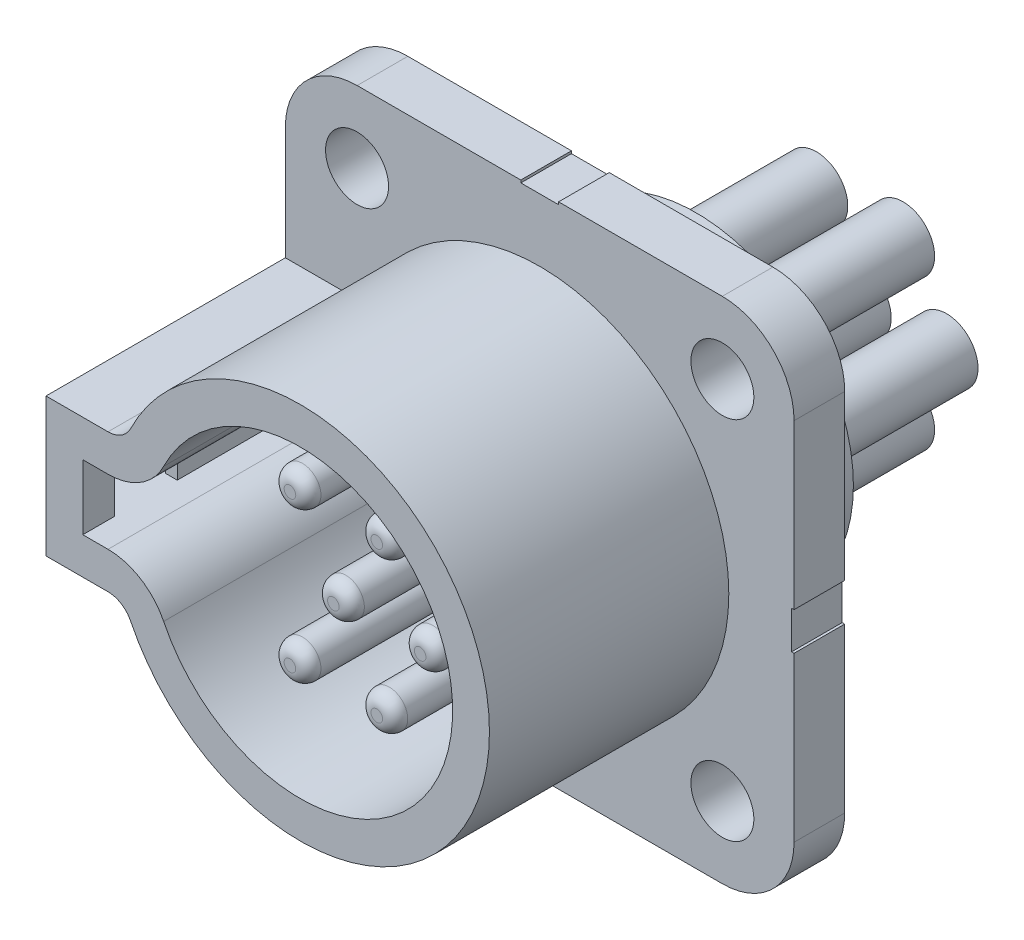
SolidWorks part; units mm, degrees
ref_plane "Front Plane" through (0, 0, 0) normal (0, 0, 1) x (1, 0, 0)
ref_plane "Top Plane" through (0, 0, 0) normal (0, 1, 0) x (1, 0, 0)
ref_plane "Right Plane" through (0, 0, 0) normal (1, 0, 0) x (0, 0, -1)
sketch "Sketch1" plane through (0, 0, 0) normal (0, 0, 1) x (1, 0, 0)
  line L1 (-10.095, 10.095) -> (10.095, 10.095)
  line L2 (-10.095, 10.095) -> (-10.095, -10.095)
  line L3 (-10.095, -10.095) -> (10.095, -10.095)
  line L4 (10.095, 10.095) -> (10.095, -10.095)
  line L5 (-10.095, 10.095) -> (10.095, -10.095) construction
  line L6 (-10.095, -10.095) -> (10.095, 10.095) construction
  point P0 (0, 0)
  dimension "D1" = 20.19
  dimension "D2" = 20.19
extrude "Boss-Extrude1" add sketch "Sketch1" along normal blind 2.01
sketch "Sketch2" plane through (0, 0, 2.01) normal (0, 0, 1) x (1, 0, 0)
  line L0 (0, 0) -> (0, 10.095) construction
  line L1 (10.095, 10.095) -> (-10.095, 10.095) construction
  line L2 (0, 0) -> (-10.095, 0) construction
  line L3 (-10.095, 10.095) -> (-10.095, -10.095) construction
  circle A0 centre (-7.25, 7.25) radius 1.25
  circle A1 centre (7.25, 7.25) radius 1.25
  circle A2 centre (7.25, -7.25) radius 1.25
  circle A3 centre (-7.25, -7.25) radius 1.25
  dimension "D1" = 2.5
  dimension "D2" = 7.25
  dimension "D3" = 7.25
extrude "Cut-Extrude1" cut sketch "Sketch2" against normal up to surface (2.01 mm away) up to face at (0, 0, 0)
fillet "Fillet1" radius 2.85 4 edges at (10.095, -10.095, 1.005) (-10.095, -10.095, 1.005) (10.095, 10.095, 1.005) (-10.095, 10.095, 1.005)
sketch "Sketch4" plane through (0, 0, 2.01) normal (0, 0, 1) x (1, 0, 0)
  line L0 (-10.095, -2.7495) -> (-10.095, 2.7495)
  line L1 (-10.095, 7.245) -> (-10.095, -7.245) construction
  line L2 (-10.095, 2.7495) -> (-7.6339, 2.7495)
  line L3 (-10.095, 0) -> (11.2357, 0) construction
  line L4 (-10.095, -2.7495) -> (-7.6339, -2.7495)
  line L5 (-8.635, -1.2895) -> (-8.635, 1.2895)
  line L6 (-8.635, 1.2895) -> (-7.6339, 1.2895)
  line L7 (-8.635, -1.2895) -> (-7.6339, -1.2895)
  line L8 (0, 10.095) -> (0, -11.6505) construction
  line L9 (7.245, 10.095) -> (-7.245, 10.095) construction
  line L10 (0, 6.045) -> (3.3385, 6.045) construction
  line L11 (0, -6.045) -> (3.3385, -6.045) construction
  line L12 (0, -7.505) -> (3.9298, -7.505) construction
  line L13 (0, 7.505) -> (4.2254, 7.505) construction
  arc A0 (-6.7363, 3.3086) -> (-6.7363, -3.3086) centre (0, 0) cw
  arc A1 (-6.7363, 3.3086) -> (-7.6339, 2.7495) centre (-7.6339, 3.7495) cw
  arc A2 (-6.7363, -3.3086) -> (-7.6339, -2.7495) centre (-7.6339, -3.7495) ccw
  arc A3 (-5.4259, 2.665) -> (-7.6339, 1.2895) centre (-7.6339, 3.7495) cw
  arc A4 (-5.4259, 2.665) -> (-5.4259, -2.665) centre (0, 0) cw
  arc A5 (-5.4259, -2.665) -> (-7.6339, -1.2895) centre (-7.6339, -3.7495) ccw
  dimension "D1" = 1
  dimension "D3" = 15.01
  dimension "D4" = 12.09
extrude "Boss-Extrude2" add sketch "Sketch4" along normal blind 9.5
sketch "Sketch5" plane through (-10.095, 0, 0) normal (-1, 0, 0) x (0, 0, 1)
  line L0 (0, 7.245) -> (0, -7.245) construction
  line L1 (0, 1.2895) -> (10.26, 1.2895)
  line L2 (0, 1.2895) -> (0, -1.2895)
  line L3 (0, -1.2895) -> (10.26, -1.2895)
  line L4 (10.26, 1.2895) -> (10.26, -1.2895)
  line L6 (0, 0) -> (-1.0293, 0) construction
  line L7 (11.51, 2.7495) -> (11.51, -2.7495) construction
  line L8 (11.51, 2.7495) -> (2.01, 2.7495) construction
  line L9 (11.51, -2.7495) -> (2.01, -2.7495) construction
  dimension "D1" = 1.25
  dimension "D2" = 1.46
  dimension "D3" = 1.46
extrude "Cut-Extrude2" cut sketch "Sketch5" against normal blind 1
sketch "Sketch6" plane through (-9.095, 0, 0) normal (-1, 0, 0) x (0, 0, 1)
  line L0 (0, -1.2895) -> (10.26, -1.2895) construction
  line L1 (10.26, 1.2895) -> (7.76, 1.2895)
  line L2 (10.26, 1.2895) -> (10.26, -1.2895)
  line L3 (10.26, -1.2895) -> (7.76, -1.2895)
  line L4 (7.76, 1.2895) -> (7.76, -1.2895)
  dimension "D1" = 2.5
extrude "Cut-Extrude3" cut sketch "Sketch6" against normal up to next
sketch "Sketch7" plane through (0, 0, 0) normal (0, 0, -1) x (-1, 0, 0)
  circle A0 centre (0, 0) radius 6.25
  dimension "D1" = 12.5
extrude "Boss-Extrude3" add sketch "Sketch7" along normal blind 4.19
sketch "Sketch8" plane through (0, 0, 2.01) normal (0, 0, 1) x (1, 0, 0)
  line L0 (-3.445, 0) -> (5.0962, 0) construction
  circle A0 centre (0, 0) radius 0.73
  circle A2 centre (3.445, 0) radius 0.73
  circle A3 centre (1.7225, 2.9835) radius 0.73
  circle A4 centre (-1.7225, 2.9835) radius 0.73
  circle A5 centre (1.7225, -2.9835) radius 0.73
  circle A6 centre (-1.7225, -2.9835) radius 0.73
  dimension "D1" = 1.46
extrude "Boss-Extrude4" add sketch "Sketch8" along normal blind 8.19 and the other way blind 7
fillet "Fillet2" radius 0.5 6 edges at (-2.4525, -2.9835, 10.2) (2.4525, 2.9835, 10.2) (0.9925, -2.9835, 10.2) (4.175, 0, 10.2) (0.73, 0, 10.2) (-0.9925, 2.9835, 10.2)
sketch "Sketch9" plane through (0, 0, -4.19) normal (0, 0, -1) x (-1, 0, 0)
  circle A0 centre (-1.7225, 2.9835) radius 1
  circle A1 centre (1.7225, 2.9835) radius 1
  circle A2 centre (0, 0) radius 1
  circle A3 centre (-3.445, 0) radius 1
  circle A4 centre (-1.7225, -2.9835) radius 1
  circle A5 centre (-1.7225, -2.9835) radius 1
  circle A6 centre (1.7225, -2.9835) radius 1
  point P0 (-1.7225, 2.9835)
  point P1 (1.7225, 2.9835)
  point P3 (-3.445, 0)
  point P5 (0, 0)
  point P7 (-1.7225, -2.9835)
  point P9 (1.7225, -2.9835)
  dimension "D1" = 2
  dimension "D2" = 2
  dimension "D3" = 2
  dimension "D4" = 2
  dimension "D5" = 2
  dimension "D6" = 2
extrude "Extrude-Thin1" add sketch "Sketch9" along normal blind 6.5 thin contours A0 | A1 | A2 | A3 | A4 | A6 thin type one direction wall 0.25
sketch "Sketch10" plane through (0, 10.095, 0) normal (0, 1, 0) x (1, 0, 0)
  line L0 (7.245, 0) -> (-7.245, 0) construction
  line L1 (-0.75, 0) -> (0.75, 0)
  line L2 (-0.75, 0) -> (-0.75, -2.01)
  line L3 (-0.75, -2.01) -> (0.75, -2.01)
  line L4 (0.75, 0) -> (0.75, -2.01)
  line L5 (7.245, -2.01) -> (-7.245, -2.01) construction
  line L6 (0, 4.99) -> (0, -4.274) construction
  line L7 (0.73, 4.99) -> (-0.73, 4.99) construction
  point P10 (0, -2.01)
  dimension "D1" = 1.5
  dimension "D2" = 0
extrude "Cut-Extrude4" cut sketch "Sketch10" against normal blind 0.1
sketch "Sketch12" plane through (10.095, 0, 0) normal (1, 0, 0) x (0, 0, -1)
  line L0 (-11.51, 0) -> (5.9037, 0)
  line L1 (-11.51, 7.505) -> (-11.51, -7.505) construction
  line L2 (0, -7.245) -> (0, 7.245) construction
  line L3 (-2.01, 0.75) -> (0, 0.75)
  line L4 (-2.01, 0.75) -> (-2.01, -0.75)
  line L5 (-2.01, -0.75) -> (0, -0.75)
  line L6 (0, 0.75) -> (0, -0.75)
  line L7 (-2.01, 0.75) -> (0, -0.75) construction
  line L8 (-2.01, -0.75) -> (0, 0.75) construction
  line L9 (-2.01, -7.245) -> (-2.01, 7.245) construction
  point P5 (-1.005, 0)
  dimension "D1" = 1.5
extrude "Cut-Extrude5" cut sketch "Sketch12" against normal blind 0.1 contours L3 L6 L5 L4
sketch "Sketch13" plane through (0, 0, -10.69) normal (0, 0, -1) x (-1, 0, 0)
  line L2 (1.7225, 2.9835) -> (0.3513, 2.9835) construction
  line L5 (1.7225, 2.9835) -> (1.7225, 3.6946) construction
  line L6 (2.9438, 3.2498) -> (2.9438, 2.7172)
  line L7 (2.9725, 2.7172) -> (2.9438, 2.7172)
  line L8 (2.9725, 3.2498) -> (2.9438, 3.2498)
  line L9 (2.9725, 2.7172) -> (2.9725, 3.2498)
extrude "Boss-Extrude5" add sketch "Sketch13" against normal up to surface (6.5 mm away) up to face at (-2.9725, -2.9835, -4.19)
equation "\"D2@Sketch1\"=\"D1@Sketch1\""
equation "\"D3@Sketch5\"=\"D2@Sketch5\""
equation "\"D2@Sketch9\"=\"D1@Sketch9\""
equation "\"D3@Sketch9\"=\"D1@Sketch9\""
equation "\"D4@Sketch9\"=\"D1@Sketch9\""
equation "\"D5@Sketch9\"=\"D1@Sketch9\""
equation "\"D6@Sketch9\"=\"D1@Sketch9\""
